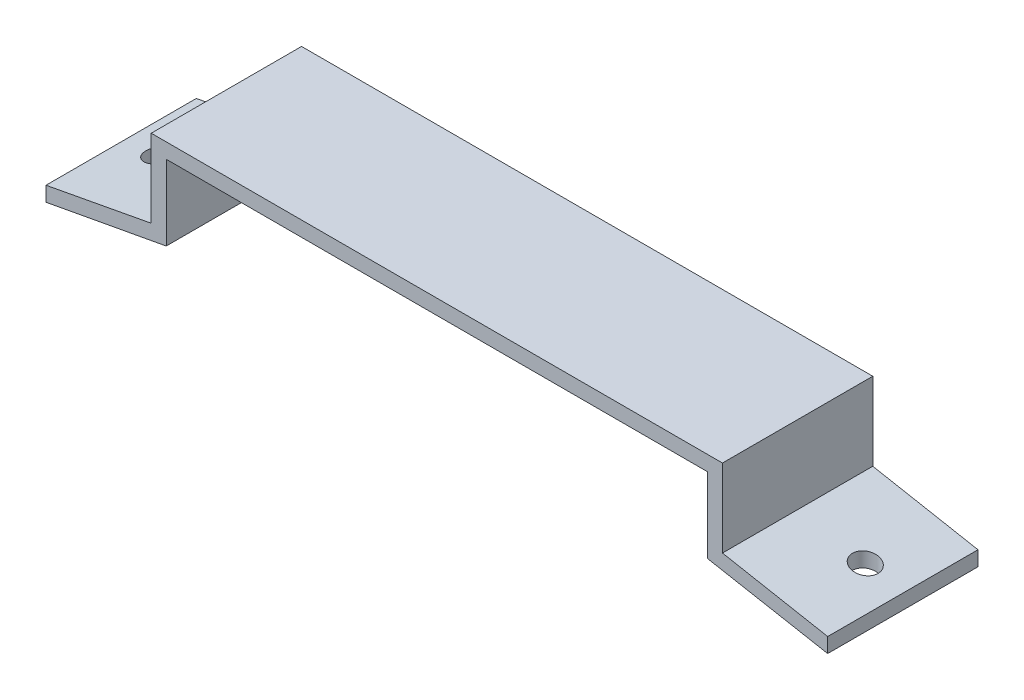
SolidWorks part; units mm, degrees
ref_plane "Plan de face" through (0, 0, 0) normal (0, 0, 1) x (1, 0, 0)
ref_plane "Plan de dessus" through (0, 0, 0) normal (0, 1, 0) x (1, 0, 0)
ref_plane "Plan de droite" through (0, 0, 0) normal (1, 0, 0) x (0, 0, -1)
sketch "Esquisse1" plane through (0, 0, 0) normal (0, 1, 0) x (1, 0, 0)
  line L1 (-52, 10) -> (0, 10)
  line L2 (-52, 10) -> (-52, -10)
  line L3 (-52, -10) -> (0, -10)
  line L4 (0, 10) -> (0, -10)
  line L5 (-28.6, 0) -> (28.6, 0) construction
  line L6 (0, -11) -> (0, 11) construction
  line L7 (-36, 10) -> (-36, -10)
  line L8 (-38, 10) -> (-38, -10)
  circle A0 centre (-47, 0) radius 1.7
  point P7 (0, 0)
  dimension "D3" = 3.4
  dimension "D1" = 20
  dimension "D2" = 5
  dimension "D4" = 36
  dimension "D5" = 2
  dimension "D6" = 47
sketch "Esquisse3" plane through (0, 0, 0) normal (0, 0, 1) x (1, 0, 0)
  line L0 (-36, 0) -> (-52, -2.9584)
  line L1 (-36, 0) -> (-36, 2) construction
  line L2 (-52, 0) -> (-47, 0) construction
  line L3 (-45.3, 0) -> (-48.7, 0) construction
  line L4 (-36, 2) -> (-52, -0.9927)
  line L5 (-52, -0.9927) -> (-52, -2.9584)
  line L6 (-36, 0) -> (-36, 2)
  point P2 (0, 0)
  dimension "D1" = 2
  dimension "D2" = 5
  dimension "D3" = 2
extrude "Boss.-Extru.5" add sketch "Esquisse3" along normal mid plane 20
extrude "Boss.-Extru.6" add sketch "Esquisse1" along normal blind 12 contours L1 L7 L3 L4 | L1 L8 L3 L7 region at (-37, 0, 0) region at (-18, 0, 0)
extrude "Enlèv. mat.-Extru.4" cut sketch "Esquisse1<9>" along normal blind 10 contours L1 L7 L3 L4 region at (-18, 0, 0)
sketch "Esquisse1<9>" plane through (0, 0, 0) normal (0, 1, 0) x (1, 0, 0) same geometry as "Esquisse1"
extrude "Enlèv. mat.-Extru.5" cut sketch "Esquisse1<10>" against normal through all both and the other way through all contours A0 region at (-47, 0, 0)
sketch "Esquisse1<10>" plane through (0, 0, 0) normal (0, 1, 0) x (1, 0, 0) same geometry as "Esquisse1"
mirror "Symétrie4" about plane through (0, 0, 0) normal (1, 0, 0) of "Enlèv. mat.-Extru.5", "Enlèv. mat.-Extru.4", "Boss.-Extru.6", "Boss.-Extru.5"
